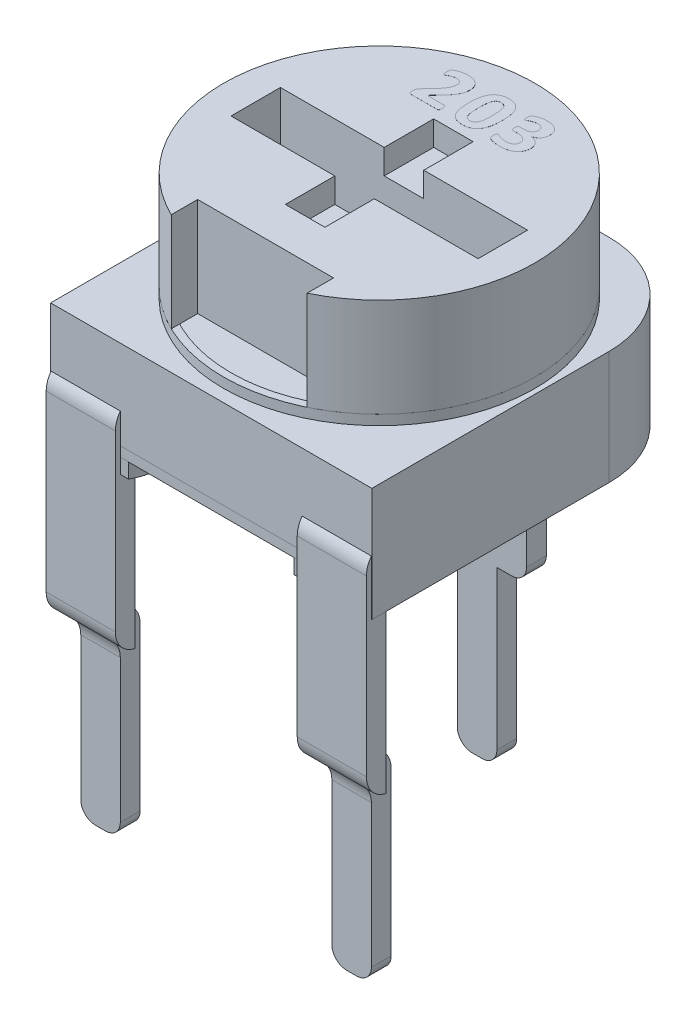
SolidWorks part; units mm, degrees
material "ABS"
ref_plane "Front Plane" through (0, 0, 0) normal (0, 0, 1) x (1, 0, 0)
ref_plane "Top Plane" through (0, 0, 0) normal (0, 1, 0) x (1, 0, 0)
ref_plane "Right Plane" through (0, 0, 0) normal (1, 0, 0) x (0, 0, -1)
sketch "Sketch1" plane through (0, 0, 0) normal (0, 1, 0) x (1, 0, 0)
  line L0 (0, 3.15) -> (0, -3.15) construction
  line L1 (0, 3.15) -> (0, 3.4) construction
  line L2 (0, -3.15) -> (0, -3.4) construction
  line L3 (-3.15, 0) -> (3.15, 0) construction
  line L4 (3.15, 0) -> (3.25, 0) construction
  line L5 (-3.15, 0) -> (-3.25, 0) construction
  line L6 (-3.25, -3.4) -> (3.25, -3.4)
  line L7 (-3.25, -3.4) -> (-3.25, 3.4)
  line L8 (-3.25, 3.4) -> (3.25, 3.4)
  line L9 (3.25, 3.4) -> (3.25, -3.4)
  circle A0 centre (0, 0) radius 3.15 construction
  dimension "D1" = 6.3
  dimension "D2" = 6.8
  dimension "D3" = 6.5
extrude "Boss-Extrude1" add sketch "Sketch1" along normal blind 2.3
sketch "Sketch2" plane through (0, 2.3, 0) normal (0, 1, 0) x (1, 0, 0)
  circle A0 centre (0, 0) radius 3.15 construction
  circle A1 centre (0, 0) radius 3.15
extrude "Boss-Extrude2" add sketch "Sketch2" along normal blind 0.2
fillet "Fillet1" radius 2 2 edges at (3.25, 1.15, -3.4) (-3.25, 1.15, -3.4)
sketch "Sketch3" plane through (0, 0, 0) normal (0, -1, 0) x (1, 0, 0)
  line L0 (0, 0) -> (0, -2.5) construction
  line L1 (-1.75, -2.5) -> (1.75, -2.5)
  line L6 (-2.25, -2) -> (-2.25, 2)
  line L7 (2.25, -2) -> (2.25, 2)
  line L8 (-2.25, 2) -> (-3, 2)
  line L9 (-3, 2) -> (-3, 3.4)
  line L10 (-3.25, 3.4) -> (3.25, 3.4) construction
  line L11 (2.25, 2) -> (3, 2)
  line L12 (3, 2) -> (3, 3.4)
  line L13 (3, 3.4) -> (-3, 3.4)
  line L14 (0, 0) -> (0, 3.4) construction
  arc A0 (-1.75, -2.5) -> (-2.25, -2) centre (-1.75, -2) cw
  arc A1 (1.75, -2.5) -> (2.25, -2) centre (1.75, -2) ccw
  point P20 (2.25, -2.5)
  dimension "D6" = 0.5
  dimension "D1" = 4.5
  dimension "D2" = 2.5
  dimension "D3" = 4.5
  dimension "D4" = 1.4
  dimension "D5" = 6
extrude "Cut-Extrude1" cut sketch "Sketch3" against normal blind 0.5
sketch "Sketch4" plane through (0, 0.5, 0) normal (0, -1, 0) x (1, 0, 0)
  line L8 (-3, 2) -> (-2.25, 2)
  line L9 (-2.25, 2) -> (-2.25, -2)
  line L10 (-1.75, -2.5) -> (1.75, -2.5)
  line L11 (2.25, -2) -> (2.25, 2)
  line L12 (2.25, 2) -> (3, 2)
  line L13 (3, 2) -> (3, 3.4)
  line L14 (3, 3.4) -> (-3, 3.4)
  line L15 (-3, 3.4) -> (-3, 2)
  line L16 (-3, 2) -> (-2.25, 2)
  line L17 (-2.25, 2) -> (-2.25, -2)
  line L18 (-1.75, -2.5) -> (1.75, -2.5)
  line L19 (2.25, -2) -> (2.25, 2)
  line L20 (2.25, 2) -> (3, 2)
  line L21 (3, 2) -> (3, 3.4)
  line L22 (3, 3.4) -> (-3, 3.4)
  line L23 (-3, 3.4) -> (-3, 2)
  arc A2 (-2.25, -2) -> (-1.75, -2.5) centre (-1.75, -2) ccw
  arc A3 (1.75, -2.5) -> (2.25, -2) centre (1.75, -2) ccw
  arc A4 (-2.25, -2) -> (-1.75, -2.5) centre (-1.75, -2) ccw
  arc A5 (1.75, -2.5) -> (2.25, -2) centre (1.75, -2) ccw
  dimension "D1" = 0
extrude "Boss-Extrude3" add sketch "Sketch4" along normal blind 0.2 separate body
sketch "Sketch5" plane through (0, 0.3, 0) normal (0, -1, 0) x (1, 0, 0)
  line L0 (0, 3.4) -> (0, 2.9) construction
  line L1 (3, 3.4) -> (-3, 3.4) construction
  line L2 (0, 2.9) -> (0, -2.18) construction
  line L3 (-2.54, 2.9) -> (2.54, 2.9) construction
  circle A0 centre (2.54, 2.9) radius 1
  circle A1 centre (-2.54, 2.9) radius 1
  circle A2 centre (0, -2.18) radius 1
  dimension "D2" = 5.08
  dimension "D4" = 2
  dimension "D1" = 0.5
  dimension "D3" = 5.08
extrude "Boss-Extrude4" add sketch "Sketch5" along normal up to surface (0.3 mm away) up to face at (0, 0, 0.1228)
sketch "Sketch6" plane through (0, 0.3, 0) normal (0, 1, 0) x (1, 0, 0)
  line L0 (-3.25, -3.4) -> (-3.25, -1)
  line L1 (-3.25, 1.4) -> (-3.25, -3.4) construction
  line L2 (-3.25, -1) -> (-4.35, -1)
  line L3 (-4.35, -1) -> (-4.35, -4.5)
  line L4 (-4.35, -4.5) -> (4.35, -4.5)
  line L5 (4.35, -4.5) -> (4.35, -1)
  line L6 (4.35, -1) -> (3.25, -1)
  line L7 (3.25, -3.4) -> (3.25, 1.4) construction
  line L8 (-3.25, -3.4) -> (3.25, -3.4)
  line L9 (3.25, -3.4) -> (3.25, -1)
  line L10 (0, 0) -> (0, -3.4) construction
  line L11 (0, -3.4) -> (0, -4.5) construction
  dimension "D1" = 3.5
extrude "Cut-Extrude2" cut sketch "Sketch6" against normal up to surface (0.3 mm away) up to face at (0, 0, -0.817)
sketch "Sketch8" plane through (0, 0.3, 0) normal (0, -1, 0) x (1, 0, 0)
  line L1 (-0.4, -1.98) -> (0.4, -1.98)
  line L2 (-0.4, -1.98) -> (-0.4, -2.38)
  line L3 (-0.4, -2.38) -> (0.4, -2.38)
  line L4 (0.4, -1.98) -> (0.4, -2.38)
  line L5 (-0.4, -1.98) -> (0.4, -2.38) construction
  line L6 (-0.4, -2.38) -> (0.4, -1.98) construction
  line L7 (-2.94, 3.1) -> (-2.14, 3.1)
  line L8 (-2.94, 3.1) -> (-2.94, 2.7)
  line L9 (-2.94, 2.7) -> (-2.14, 2.7)
  line L10 (-2.14, 3.1) -> (-2.14, 2.7)
  line L11 (-2.94, 3.1) -> (-2.14, 2.7) construction
  line L12 (-2.94, 2.7) -> (-2.14, 3.1) construction
  line L13 (2.94, 3.1) -> (2.14, 3.1)
  line L14 (2.94, 3.1) -> (2.94, 2.7)
  line L15 (2.94, 2.7) -> (2.14, 2.7)
  line L16 (2.14, 3.1) -> (2.14, 2.7)
  line L17 (2.94, 3.1) -> (2.14, 2.7) construction
  line L18 (2.94, 2.7) -> (2.14, 3.1) construction
  point P0 (0, -2.18)
  point P5 (-2.54, 2.9)
  point P11 (2.54, 2.9)
  dimension "D1" = 0.4
  dimension "D2" = 0.8
extrude "Boss-Extrude5" add sketch "Sketch8" along normal blind 7
sketch "Sketch9" plane through (0, 0.3, 0) normal (0, -1, 0) x (1, 0, 0)
  line L4 (0, -1.98) -> (0, -2.38) construction
  line L5 (0.4, -1.98) -> (-0.4, -1.98) construction
  line L6 (-0.4, -2.38) -> (0.4, -2.38) construction
  line L8 (-1, -1.98) -> (1, -1.98)
  line L9 (-1, -1.98) -> (-1, -2.38)
  line L10 (-1, -2.38) -> (1, -2.38)
  line L11 (1, -1.98) -> (1, -2.38)
  line L12 (-1, -1.98) -> (1, -2.38) construction
  line L13 (-1, -2.38) -> (1, -1.98) construction
  point P14 (0, -2.18)
  dimension "D1" = 2
extrude "Boss-Extrude6" add sketch "Sketch9" along normal blind 3.5
sketch "Sketch10" plane through (0, 0.3, 0) normal (0, -1, 0) x (1, 0, 0)
  line L0 (-2.54, 3.1) -> (-2.54, 3.5) construction
  line L1 (-2.14, 3.1) -> (-2.94, 3.1) construction
  line L2 (2.54, 3.1) -> (2.54, 3.5) construction
  line L3 (2.94, 3.1) -> (2.14, 3.1) construction
  line L4 (-2.94, 3.1) -> (-2.94, 2.7) construction
  line L5 (-3.24, 3.5) -> (-1.84, 3.5)
  line L6 (-3.24, 3.5) -> (-3.24, 3.1)
  line L7 (-3.24, 3.1) -> (-1.84, 3.1)
  line L8 (-1.84, 3.5) -> (-1.84, 3.1)
  line L10 (1.84, 3.5) -> (3.24, 3.5)
  line L11 (1.84, 3.5) -> (1.84, 3.1)
  line L12 (1.84, 3.1) -> (3.24, 3.1)
  line L13 (3.24, 3.5) -> (3.24, 3.1)
  dimension "D1" = 1.4
extrude "Boss-Extrude7" add sketch "Sketch10" along normal blind 3.5 and the other way blind 1
fillet "Fillet2" radius 0.5 2 edges at (2.54, 1.3, 3.5) (-2.54, 1.3, 3.5)
sketch "Sketch11" plane through (0, 0, 0) normal (1, 0, 0) x (0, 0, -1)
  line L0 (-3.4, 0) -> (1.4, 0) construction
  line L1 (-3.1, -2.8) -> (-2.7, -2.8)
  line L2 (-3.1, -2.8) -> (-3.1, 0)
  line L3 (-3.1, 0) -> (-2.7, 0)
  line L4 (-2.7, -2.8) -> (-2.7, 0)
  line L5 (-2.7, -6.7) -> (-2.7, 0.3) construction
  line L6 (-3.1, -2.8) -> (-3.1, -3.2) construction
extrude "Cut-Extrude3" cut sketch "Sketch11" against normal through all both and the other way through all
fillet "Fillet3" radius 0.5 4 edges at (-2.54, -2.8, 3.1) (2.54, -2.8, 3.1) (-2.54, -3.2, 3.5) (2.54, -3.2, 3.5)
fillet "Fillet4" radius 0.5 4 edges at (2.54, -2.8, 2.7) (-2.54, -2.8, 2.7) (2.54, -3.2, 3.1) (-2.54, -3.2, 3.1)
fillet "Fillet5" radius 0.3 12 edges at (-1, -3.2, -2.18) (1, -3.2, -2.18) (-0.4, -6.7, -2.18) (0.4, -6.7, -2.18) (2.14, -6.7, 2.9) (2.94, -6.7, 2.9) (-2.94, -6.7, 2.9) (-2.14, -6.7, 2.9) (-2.14, -2.7551, 3.1) (-2.94, -2.7551, 3.1) (2.14, -2.7551, 3.1) (2.94, -2.7551, 3.1)
sketch "Sketch12" plane through (0, 0.3, 0) normal (0, -1, 0) x (1, 0, 0)
  circle A0 centre (0, 0) radius 2
  circle A1 centre (0, 0) radius 1.5
  dimension "D1" = 4
  dimension "D2" = 3
extrude "Boss-Extrude8" add sketch "Sketch12" along normal blind 0.15
sketch "Sketch15" plane through (0, 2.5, 0) normal (0, 1, 0) x (1, 0, 0)
  circle A0 centre (0, 0) radius 3
  dimension "D1" = 6
extrude "Cut-Extrude4" cut sketch "Sketch15" against normal blind 0.5
sketch "Sketch14" plane through (0, 2.5, 0) normal (0, 1, 0) x (1, 0, 0)
  circle A1 centre (0, 0) radius 3.15
  circle A2 centre (0, 0) radius 3.15
  dimension "D1" = 0
extrude "Boss-Extrude9" add sketch "Sketch14" along normal blind 2 separate body
sketch "Set Angle of Knob" plane through (0, 4.5, 0) normal (0, 1, 0) x (1, 0, 0)
  line L0 (0, 0) -> (0, -3.15) construction
  line L1 (-2.5, 0) -> (2.5, 0) construction
  line L2 (-2.5, 0.5) -> (-2.5, -0.5)
  line L3 (2.5, 0.5) -> (2.5, -0.5)
  line L4 (-2.5, 0.5) -> (-0.4, 0.5)
  line L5 (-2.5, -0.5) -> (-0.4, -0.5)
  line L6 (0, 0) -> (0, -1.5) construction
  line L7 (0, 0) -> (0, 1.5) construction
  line L8 (0, 1.5) -> (0, 3.15) construction
  line L9 (0.4, 1.5) -> (-0.4, 1.5)
  line L10 (0.4, 1.5) -> (0.4, 0.5)
  line L11 (-0.4, 1.5) -> (-0.4, 0.5)
  line L12 (0.4, 0.5) -> (2.5, 0.5)
  line L13 (-0.4, -1.5) -> (0.4, -1.5)
  line L14 (-0.4, -1.5) -> (-0.4, -0.5)
  line L15 (0.4, -1.5) -> (0.4, -0.5)
  line L16 (0.4, -0.5) -> (2.5, -0.5)
  line L17 (0, -1.5) -> (0, -2.3) construction
  line L18 (-1.375, -2.3) -> (1.375, -2.3)
  line L19 (-1.375, -2.3) -> (-1.375, -3.8)
  line L20 (1.375, -2.3) -> (1.375, -3.8)
  line L21 (-1.375, -3.8) -> (1.375, -3.8)
  line L22 (-1, 0.25) -> (1, 0.25) construction
  line L23 (-1, 0.25) -> (-1, -0.25) construction
  line L24 (-1, -0.25) -> (1, -0.25) construction
  line L25 (1, -0.25) -> (1, 0.25) construction
  circle A0 centre (0, 0) radius 3.15 construction
  circle A1 centre (0, 0) radius 3.15 construction
  point P32 (0, 0.25)
  dimension "D1" = 1
  dimension "D2" = 0.8
  dimension "D3" = 1.5
  dimension "D4" = 5
  dimension "D5" = 90
  dimension "D6" = 2.75
  dimension "D7" = 1.5
  dimension "D8" = 1.8
  dimension "D9" = 0.25
  dimension "D10" = 0.25
  dimension "D11" = 2
extrude "TURN KNOB" cut sketch "Set Angle of Knob" against normal blind 2.3
sketch "Sketch17" plane through (0, 2, 0) normal (0, 1, 0) x (1, 0, 0)
  line L0 (-0.4, -1.5) -> (0.4, -1.5)
  line L1 (0.4, -1.5) -> (0.4, -0.5)
  line L2 (0.4, 1.5) -> (-0.4, 1.5)
  line L3 (-0.4, 1.5) -> (-0.4, 0.5)
  line L4 (-0.4, 0.5) -> (0.4, 0.5)
  line L5 (-0.4, -0.5) -> (0.4, -0.5)
  line L6 (-0.4, -0.5) -> (-0.4, -1.5)
  line L7 (0.4, 0.5) -> (0.4, 1.5)
extrude "Boss-Extrude10" add sketch "Sketch17" along normal blind 2
sketch "Sketch20" plane through (0, 2, 0) normal (0, 1, 0) x (1, 0, 0)
  line L0 (-1, 0.25) -> (1, 0.25) construction
  line L1 (-1, 0.25) -> (1, 0.25)
  line L2 (-1, -0.25) -> (1, -0.25) construction
  line L3 (-1, -0.25) -> (1, -0.25)
  line L4 (-1, 0.25) -> (-1, -0.25) construction
  line L5 (-1, 0.25) -> (-1, -0.25)
  line L6 (1, -0.25) -> (1, 0.25) construction
  line L7 (1, -0.25) -> (1, 0.25)
extrude "Cut-Extrude6" cut sketch "Sketch20" against normal blind 0.5
fillet "Fillet6" radius 0.2 2 edges at (1, 2, 0) (-1, 2, 0)
sketch "See Code in Properties" plane through (0, 4.5, 0) normal (0, 1, 0) x (1, 0, 0)
  line L0 (0, 1.5) -> (0, 1.7) construction
  line L1 (0.4, 1.5) -> (-0.4, 1.5) construction
  line L2 (0, 1.5) -> (0, 3.15) construction
  line L3 (-1.5, 1.7) -> (1.5, 1.7) construction
  text T0 "203" font "Calibri" height 0.9
  dimension "D1" = 0.2
  dimension "D2" = 3
extrude "Code Number" add sketch "See Code in Properties" along normal blind 0.001
